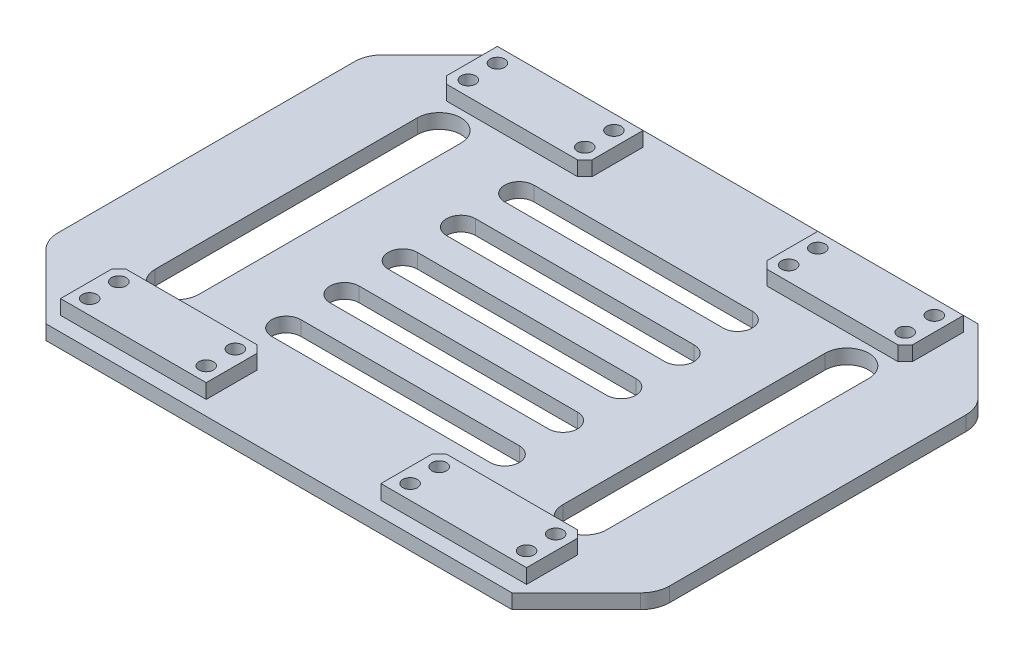
SolidWorks part; units mm, degrees
ref_plane "Front Plane" through (0, 0, 0) normal (0, 0, 1) x (1, 0, 0)
ref_plane "Top Plane" through (0, 0, 0) normal (0, 1, 0) x (1, 0, 0)
ref_plane "Right Plane" through (0, 0, 0) normal (1, 0, 0) x (0, 0, -1)
sketch "Sketch1" plane through (0, 0, 0) normal (0, 0, 1) x (1, 0, 0)
  circle A0 centre (0, 0) radius 18.5
  dimension "D1" = 37
extrude "Boss-Extrude1" add sketch "Sketch1" along normal blind 22.5
sketch "Sketch2" plane through (0, 0, 22.5) normal (0, 0, 1) x (1, 0, 0)
  line L0 (-18.5, 0) -> (18.5, 0) construction
  line L1 (0, 18.5) -> (0, -18.5) construction
  line L2 (11.1332, 19.2832) -> (-10.7359, -18.5952) construction
  line L3 (-11.3747, 19.7016) -> (11.6905, -20.2486) construction
  circle A0 centre (0, 0) radius 18.5 construction
  circle A1 centre (0, 0) radius 15.5 construction
  circle A2 centre (-7.75, 13.4234) radius 1.6
  circle A3 centre (7.75, 13.4234) radius 1.6
  circle A4 centre (-15.5, 0) radius 1.6
  circle A5 centre (-7.75, -13.4234) radius 1.6
  circle A6 centre (7.75, -13.4234) radius 1.6
  circle A7 centre (15.5, 0) radius 1.6
  dimension "D3" = 31
  dimension "D4" = 3.2
  dimension "D1" = 120
  dimension "D2" = 120
extrude "Cut-Extrude1" cut sketch "Sketch2" against normal blind 3.5
sketch "Sketch3" plane through (0, 0, 22.5) normal (0, 0, 1) x (1, 0, 0)
  line L0 (0, 0) -> (0, 18.5) construction
  circle A0 centre (0, 0) radius 18.5 construction
  circle A1 centre (0, 7) radius 6
  circle A2 centre (0, 7) radius 3
  dimension "D1" = 12
  dimension "D3" = 6
  dimension "D2" = 7
extrude "Boss-Extrude2" add sketch "Sketch3" along normal blind 36.3 contours A2 L0 | L0 A2 region at (-1.2732, 7, 22.5) region at (1.2732, 7, 22.5)
extrude "Boss-Extrude3" add sketch "Sketch3<3>" along normal blind 6.3 contours A1 L0 A2 | L0 A1 A2 region at (-5.8658, 7, 22.5) region at (0.1342, 2.5, 22.5)
sketch "Sketch3<3>" plane through (0, 0, 22.5) normal (0, 0, 1) x (1, 0, 0) same geometry as "Sketch3"
sketch "Sketch4" plane through (0, 0, 0) normal (0, 0, -1) x (-1, 0, 0)
  circle A0 centre (0, 0) radius 14.5
  dimension "D1" = 29
extrude "Boss-Extrude4" add sketch "Sketch4" along normal blind 37.8
sketch "Sketch5" plane through (0, 0, -37.8) normal (0, 0, -1) x (-1, 0, 0)
  line L0 (-14.5, 0) -> (14.5, 0) construction
  circle A0 centre (0, 0) radius 5
  circle A1 centre (0, 0) radius 14.5 construction
  dimension "D1" = 10
extrude "Boss-Extrude5" add sketch "Sketch5" along normal blind 3
sketch "Sketch6" plane through (0, 0, -40.8) normal (0, 0, -1) x (-1, 0, 0)
  circle A0 centre (0, 0) radius 1
  dimension "D1" = 2
extrude "Boss-Extrude6" add sketch "Sketch6" along normal blind 9
sketch "Sketch7" plane through (0, 0, -37.8) normal (0, 0, -1) x (-1, 0, 0)
  line L0 (-14.5, 0) -> (14.5, 0) construction
  line L1 (0, 0) -> (0, -10.7163) construction
  line L2 (-12, 1.5) -> (-11.5, 1.5)
  line L3 (-12, 1.5) -> (-12, -1.5)
  line L4 (-12, -1.5) -> (-11.5, -1.5)
  line L5 (-11.5, 1.5) -> (-11.5, -1.5)
  line L6 (12, 1.5) -> (11.5, 1.5)
  line L7 (12, -1.5) -> (11.5, -1.5)
  line L8 (12, 1.5) -> (12, -1.5)
  line L9 (11.5, 1.5) -> (11.5, -1.5)
  circle A0 centre (0, 0) radius 14.5 construction
  circle A1 centre (0, 0) radius 14.5 construction
  dimension "D1" = 3
  dimension "D2" = 1.5
  dimension "D3" = 0.5
  dimension "D4" = 11.5
extrude "Boss-Extrude7" add sketch "Sketch7" along normal blind 6.5
sketch "Sketch8" plane through (12, 0, 0) normal (1, 0, 0) x (0, 0, -1)
  line L0 (42.8651, 0) -> (41.6651, 0) construction
  line L1 (42.8651, -0.3201) -> (41.6651, -0.3201)
  line L2 (42.8651, 0.3201) -> (41.6651, 0.3201)
  line L3 (42.8651, 0) -> (44.3, 0) construction
  line L4 (44.3, 1.5) -> (44.3, -1.5) construction
  arc A0 (42.8651, -0.3201) -> (42.8651, 0.3201) centre (42.8651, 0) ccw
  arc A1 (41.6651, 0.3201) -> (41.6651, -0.3201) centre (41.6651, 0) ccw
  point P2 (42.2651, 0)
  dimension "D1" = 1.2
extrude "Cut-Extrude2" cut sketch "Sketch8" against normal blind 0.5
mirror "Mirror2" about plane through (0, 0, 0) normal (1, 0, 0) of "Cut-Extrude2"
fillet "Fillet1" radius 0.5 4 edges at (-11.75, 1.5, -44.3) (-11.75, -1.5, -44.3) (11.75, 1.5, -44.3) (11.75, -1.5, -44.3)
chamfer "Chamfer1" distance 0.2 angle 45 3 edges at (18.5, 0, 22.5) (6, 7, 28.8) (3, 7, 58.8)
ref_plane "Plane1" through (0, 7, 0) normal (0, 1, 0) x (1, 0, 0)
sketch "Sketch9" plane through (0, 7, 0) normal (0, 1, 0) x (1, 0, 0)
  line L0 (0, -58.6) -> (0, -28.8) construction
  line L1 (3, -58.6) -> (-3, -58.6) construction
  line L2 (-2.8, -58.8) -> (2.8, -58.8) construction
  line L3 (-3, -28.8) -> (3, -28.8) construction
  circle A0 centre (0, -50.8) radius 1.6
  dimension "D1" = 3.2
  dimension "D2" = 8
extrude "Cut-Extrude3" cut sketch "Sketch9" against normal through all and the other way through all
sketch "Sketch10" plane through (0, 0, 22.5) normal (0, 0, 1) x (1, 0, 0)
  circle A0 centre (-7.75, 13.4234) radius 1.6
  circle A1 centre (-15.5, 0) radius 1.6
  circle A2 centre (-7.75, -13.4234) radius 1.6
  circle A3 centre (7.75, -13.4234) radius 1.6
  circle A4 centre (15.5, 0) radius 1.6
  circle A5 centre (7.75, 13.4234) radius 1.6
extrude "Boss-Extrude8" add sketch "Sketch10" along normal blind 10 separate body
sketch "Sketch11" plane through (0, 0, 22.5) normal (0, 0, 1) x (1, 0, 0)
  line L0 (-25, 25) -> (25, 25)
  line L1 (25, 25) -> (25, -35)
  line L2 (25, -35) -> (-25, -35)
  line L3 (-25, -35) -> (-25, 25)
  line L4 (0, -35) -> (0, 25) construction
  dimension "D1" = 60
  dimension "D2" = 50
  dimension "D3" = 50
  dimension "D4" = 25
extrude "Boss-Extrude9" add sketch "Sketch11" along normal blind 5
sketch "Sketch13" plane through (0, 0, 22.5) normal (0, 0, -1) x (-1, 0, 0)
  line L1 (-27.6874, 26.3272) -> (29.1382, 26.3272)
  line L2 (-27.6874, 26.3272) -> (-27.6874, -27.6572)
  line L3 (-27.6874, -27.6572) -> (29.1382, -27.6572)
  line L4 (29.1382, 26.3272) -> (29.1382, -27.6572)
  line L5 (-27.6874, 26.3272) -> (29.1382, -27.6572) construction
  line L6 (-27.6874, -27.6572) -> (29.1382, 26.3272) construction
  point P4 (0.7254, -0.665)
extrude "Cut-Extrude4" cut sketch "Sketch13" along normal blind 121
sketch "Sketch14" plane through (0, 0, 27.5) normal (0, 0, 1) x (1, 0, 0)
  circle A0 centre (-7.75, 13.4234) radius 1.6
  circle A1 centre (7.75, 13.4234) radius 1.6
  circle A2 centre (-15.5, 0) radius 1.6
  circle A3 centre (-7.75, -13.4234) radius 1.6
  circle A4 centre (7.75, -13.4234) radius 1.6
  circle A5 centre (15.5, 0) radius 1.6
  circle A6 centre (0, 7) radius 6
extrude "Cut-Extrude5" cut sketch "Sketch14" against normal through all both and the other way through all
sketch "Sketch15" plane through (0, 25, 0) normal (0, 1, 0) x (1, 0, 0)
  line L1 (-25, -22.5) -> (135, -22.5)
  line L2 (-25, -22.5) -> (-25, -182.5)
  line L3 (-25, -182.5) -> (135, -182.5)
  line L4 (135, -22.5) -> (135, -182.5)
  line L5 (-25, -22.5) -> (135, -182.5) construction
  line L6 (-25, -182.5) -> (135, -22.5) construction
  point P4 (55, -102.5)
  dimension "D1" = 160
  dimension "D2" = 160
extrude "Boss-Extrude10" add sketch "Sketch15" along normal blind 5
sketch "Sketch17" plane through (0, 30, 0) normal (0, 1, 0) x (1, 0, 0)
  line L0 (55, -22.5) -> (55, -182.5) construction
  line L1 (135, -22.5) -> (-25, -22.5) construction
  line L2 (-25, -182.5) -> (135, -182.5) construction
  line L3 (-25, -102.5) -> (135, -102.5) construction
  line L4 (-25, -22.5) -> (-25, -182.5) construction
  line L5 (135, -182.5) -> (135, -22.5) construction
ref_plane "Plane2" through (55, 0, 0) normal (1, 0, 0) x (0, 0, -1)
ref_plane "Plane3" through (0, 0, 102.5) normal (0, 0, 1) x (1, 0, 0)
mirror "Mirror3" about plane through (0, 0, 102.5) normal (0, 0, 1) of bodies 122
mirror "Mirror11" about plane through (55, 0, 0) normal (1, 0, 0) of bodies 123
chamfer "Chamfer2" distance 2.5 angle 45 3 edges at (85, 25, 25) (25, 25, 25) (25, 25, 180)
chamfer "Chamfer3" distance 2.5 angle 45 1 edges at (85, 25, 180)
sketch "Sketch18" plane through (0, 30, 0) normal (0, 1, 0) x (1, 0, 0)
  line L0 (55, -22.5) -> (55, -182.5) construction
  line L1 (135, -22.5) -> (-25, -22.5) construction
  line L2 (-25, -182.5) -> (135, -182.5) construction
  line L3 (17.5, -42.5) -> (92.5, -42.5) construction
  line L4 (17.5, -62.5) -> (92.5, -62.5) construction
  line L5 (17.5, -82.5) -> (92.5, -82.5) construction
  line L6 (17.5, -102.5) -> (92.5, -102.5) construction
  line L7 (17.5, -122.5) -> (92.5, -122.5) construction
  line L8 (17.5, -142.5) -> (92.5, -142.5) construction
  line L9 (92.5, -42.5) -> (17.5, -42.5) construction
  line L10 (92.5, -47.5) -> (17.5, -47.5)
  line L11 (92.5, -37.5) -> (17.5, -37.5)
  line L12 (17.5, -62.5) -> (92.5, -62.5) construction
  line L13 (17.5, -57.5) -> (92.5, -57.5)
  line L14 (17.5, -67.5) -> (92.5, -67.5)
  line L15 (17.5, -82.5) -> (92.5, -82.5) construction
  line L16 (17.5, -77.5) -> (92.5, -77.5)
  line L17 (17.5, -87.5) -> (92.5, -87.5)
  line L18 (17.5, -102.5) -> (92.5, -102.5) construction
  line L19 (17.5, -97.5) -> (92.5, -97.5)
  line L20 (17.5, -107.5) -> (92.5, -107.5)
  line L21 (17.5, -122.5) -> (92.5, -122.5) construction
  line L22 (17.5, -117.5) -> (92.5, -117.5)
  line L23 (17.5, -127.5) -> (92.5, -127.5)
  line L24 (17.5, -142.5) -> (92.5, -142.5) construction
  line L25 (17.5, -137.5) -> (92.5, -137.5)
  line L26 (17.5, -147.5) -> (92.5, -147.5)
  line L27 (17.5, -162.5) -> (92.5, -162.5) construction
  line L28 (92.5, -162.5) -> (17.5, -162.5) construction
  line L29 (92.5, -167.5) -> (17.5, -167.5)
  line L30 (92.5, -157.5) -> (17.5, -157.5)
  arc A0 (92.5, -47.5) -> (92.5, -37.5) centre (92.5, -42.5) ccw
  arc A1 (17.5, -37.5) -> (17.5, -47.5) centre (17.5, -42.5) ccw
  arc A2 (17.5, -57.5) -> (17.5, -67.5) centre (17.5, -62.5) ccw
  arc A3 (92.5, -67.5) -> (92.5, -57.5) centre (92.5, -62.5) ccw
  arc A4 (17.5, -77.5) -> (17.5, -87.5) centre (17.5, -82.5) ccw
  arc A5 (92.5, -87.5) -> (92.5, -77.5) centre (92.5, -82.5) ccw
  arc A6 (17.5, -97.5) -> (17.5, -107.5) centre (17.5, -102.5) ccw
  arc A7 (92.5, -107.5) -> (92.5, -97.5) centre (92.5, -102.5) ccw
  arc A8 (17.5, -117.5) -> (17.5, -127.5) centre (17.5, -122.5) ccw
  arc A9 (92.5, -127.5) -> (92.5, -117.5) centre (92.5, -122.5) ccw
  arc A10 (17.5, -137.5) -> (17.5, -147.5) centre (17.5, -142.5) ccw
  arc A11 (92.5, -147.5) -> (92.5, -137.5) centre (92.5, -142.5) ccw
  arc A12 (92.5, -167.5) -> (92.5, -157.5) centre (92.5, -162.5) ccw
  arc A13 (17.5, -157.5) -> (17.5, -167.5) centre (17.5, -162.5) ccw
  point P14 (55, -42.5)
  point P15 (55, -62.5)
  point P16 (55, -82.5)
  point P17 (55, -122.5)
  point P20 (55, -102.5)
  point P23 (55, -142.5)
  point P24 (55, -42.5)
  point P29 (55, -62.5)
  point P34 (55, -82.5)
  point P39 (55, -102.5)
  point P44 (55, -122.5)
  point P49 (55, -142.5)
  point P54 (55, -162.5)
  point P56 (55, -162.5)
  dimension "D2" = 5
  dimension "D3" = 5
  dimension "D4" = 5
  dimension "D5" = 5
  dimension "D7" = 5
  dimension "D8" = 5
  dimension "D14" = 5
  dimension "D1" = 75
  dimension "D6" = 20
  dimension "D9" = 20
  dimension "D10" = 20
  dimension "D11" = 20
  dimension "D12" = 20
  dimension "D13" = 20
  dimension "D15" = 20
extrude "Cut-Extrude6" cut sketch "Sketch18" against normal through all
sketch "Sketch19" plane through (0, 30, 0) normal (0, 1, 0) x (1, 0, 0)
  line L0 (-25, -182.5) -> (135, -182.5) construction
  line L1 (-25, -22.5) -> (-50, -22.5)
  line L2 (-25, -22.5) -> (-25, -182.5)
  line L3 (-25, -182.5) -> (-50, -182.5)
  line L4 (-50, -22.5) -> (-50, -182.5)
  line L5 (-25, -22.5) -> (-50, -182.5) construction
  line L6 (-25, -182.5) -> (-50, -22.5) construction
  line L8 (135, -22.5) -> (160, -22.5)
  line L9 (135, -22.5) -> (135, -182.5)
  line L10 (135, -182.5) -> (160, -182.5)
  line L11 (160, -22.5) -> (160, -182.5)
  line L12 (135, -22.5) -> (160, -182.5) construction
  line L13 (135, -182.5) -> (160, -22.5) construction
  point P4 (-37.5, -102.5)
  point P12 (147.5, -102.5)
  dimension "D1" = 25
extrude "Boss-Extrude11" add sketch "Sketch19" against normal up to surface (5 mm away) up to face at (55, 25, 42.5)
chamfer "Chamfer4" distance 25 angle 45 4 edges at (-50, 27.5, 22.5) (-50, 27.5, 182.5) (160, 27.5, 182.5) (160, 27.5, 22.5)
sketch "Sketch20" plane through (0, 30, 0) normal (0, 1, 0) x (1, 0, 0)
  line L0 (55, -22.5) -> (55, -182.5) construction
  line L1 (135, -22.5) -> (-25, -22.5) construction
  line L2 (-25, -182.5) -> (135, -182.5) construction
  line L3 (-50, -102.5) -> (160, -102.5) construction
  line L4 (-50, -47.5) -> (-50, -157.5) construction
  line L5 (160, -157.5) -> (160, -47.5) construction
  circle A0 centre (130, -102.5) radius 12.5
  circle A1 centre (130, -62.5) radius 7.5
  circle A2 centre (130, -142.5) radius 7.5
  circle A3 centre (-20, -142.5) radius 7.5
  circle A4 centre (-20, -102.5) radius 12.5
  circle A5 centre (-20, -62.5) radius 7.5
  point P16 (0, 0)
  point P17 (0, 0)
  point P26 (55, -102.5)
  dimension "D3" = 25
  dimension "D4" = 15
  dimension "D1" = 75
  dimension "D2" = 40
extrude "Cut-Extrude7" cut sketch "Sketch20" against normal blind 10
chamfer "Chamfer5" distance 2.5 angle 45 4 edges at (108.75, 25, 177.5) (1.25, 25, 177.5) (1.25, 25, 27.5) (108.75, 25, 27.5)
chamfer "Chamfer6" distance 2.5 angle 45 4 edges at (135, 25, 178.75) (135, 25, 26.25) (-25, 25, 26.25) (-25, 25, 178.75)
fillet "Fillet2" radius 10 4 edges at (-50, 27.5, 157.5) (-50, 27.5, 47.5) (160, 27.5, 47.5) (160, 27.5, 157.5)
sketch "Sketch21" plane through (0, -35, 0) normal (0, -1, 0) x (1, 0, 0)
  line L0 (135, 27.5) -> (135, 22.5) construction
  line L1 (85, 27.5) -> (135, 27.5)
  line L2 (85, 27.5) -> (85, 47.5)
  line L3 (85, 47.5) -> (135, 47.5)
  line L4 (135, 27.5) -> (135, 47.5)
  line L5 (85, 27.5) -> (135, 47.5) construction
  line L6 (85, 47.5) -> (135, 27.5) construction
  line L7 (55, 22.5) -> (55, 152.5338) construction
  line L8 (82.5, 22.5) -> (27.5, 22.5) construction
  line L9 (-50, 102.5) -> (115.8543, 102.5) construction
  line L10 (-50, 153.3579) -> (-50, 51.6421) construction
  line L11 (110, 37.5) -> (110, 45.6589) construction
  line L12 (110, 37.5) -> (99.3164, 37.5) construction
  line L13 (85, 157.5) -> (135, 157.5)
  line L14 (135, 177.5) -> (135, 157.5)
  line L15 (85, 177.5) -> (135, 177.5)
  line L16 (85, 177.5) -> (85, 157.5)
  line L17 (25, 177.5) -> (-25, 177.5)
  line L18 (25, 177.5) -> (25, 157.5)
  line L19 (25, 157.5) -> (-25, 157.5)
  line L20 (-25, 177.5) -> (-25, 157.5)
  line L21 (-25, 27.5) -> (-25, 47.5)
  line L22 (25, 27.5) -> (-25, 27.5)
  line L23 (25, 47.5) -> (-25, 47.5)
  line L24 (25, 27.5) -> (25, 47.5)
  circle A0 centre (90, 32.5) radius 2.5
  circle A1 centre (90, 42.5) radius 2.5
  circle A2 centre (130, 32.5) radius 2.5
  circle A3 centre (130, 42.5) radius 2.5
  circle A4 centre (90, 162.5) radius 2.5
  circle A5 centre (90, 172.5) radius 2.5
  circle A6 centre (130, 172.5) radius 2.5
  circle A7 centre (130, 162.5) radius 2.5
  circle A8 centre (-20, 162.5) radius 2.5
  circle A9 centre (-20, 172.5) radius 2.5
  circle A10 centre (20, 172.5) radius 2.5
  circle A11 centre (20, 162.5) radius 2.5
  circle A12 centre (-20, 32.5) radius 2.5
  circle A13 centre (-20, 42.5) radius 2.5
  circle A14 centre (20, 32.5) radius 2.5
  circle A15 centre (20, 42.5) radius 2.5
  point P4 (110, 37.5)
  dimension "D4" = 5
  dimension "D1" = 20
  dimension "D2" = 5
  dimension "D3" = 20
extrude "Boss-Extrude12" add sketch "Sketch21" against normal blind 5 from offset 5 offset against normal yes
chamfer "Chamfer7" distance 2.5 angle 45 8 edges at (85, -27.5, 47.5) (135, -27.5, 47.5) (-25, -27.5, 47.5) (25, -27.5, 47.5) (25, -27.5, 157.5) (-25, -27.5, 157.5) (85, -27.5, 157.5) (135, -27.5, 157.5)
sketch "Sketch22" plane through (0, -35, 0) normal (0, -1, 0) x (1, 0, 0)
  line L0 (-27.5, 180) -> (-25, 182.5)
  line L1 (-25, 182.5) -> (27.5, 182.5)
  line L2 (82.5, 182.5) -> (135, 182.5)
  line L3 (135, 182.5) -> (137.5, 180)
  line L4 (137.5, 25) -> (135, 22.5)
  line L5 (135, 22.5) -> (82.5, 22.5)
  line L6 (-27.5, 25) -> (-25, 22.5)
  line L7 (-25, 22.5) -> (27.5, 22.5)
  line L8 (-22.5, 157.5) -> (22.5, 157.5) construction
  line L9 (22.5, 157.5) -> (25, 160) construction
  line L10 (25, 160) -> (25, 177.5) construction
  line L11 (25, 177.5) -> (-25, 177.5) construction
  line L12 (-25, 177.5) -> (-25, 160) construction
  line L13 (-25, 160) -> (-22.5, 157.5) construction
  line L14 (85, 177.5) -> (85, 160) construction
  line L15 (85, 160) -> (87.5, 157.5) construction
  line L16 (87.5, 157.5) -> (132.5, 157.5) construction
  line L17 (132.5, 157.5) -> (135, 160) construction
  line L18 (135, 160) -> (135, 177.5) construction
  line L19 (135, 177.5) -> (85, 177.5) construction
  line L20 (-27.5, 180) -> (-47.0711, 160.4289)
  line L21 (-50, 153.3579) -> (-50, 51.6421)
  line L22 (-47.0711, 44.5711) -> (-27.5, 25)
  line L23 (-27.5, 25) -> (-27.5, 30)
  line L24 (-27.5, 30) -> (27.5, 30)
  line L25 (27.5, 30) -> (27.5, 22.5)
  line L26 (27.5, 22.5) -> (82.5, 22.5)
  line L27 (82.5, 22.5) -> (82.5, 30)
  line L28 (82.5, 30) -> (137.5, 30)
  line L29 (137.5, 30) -> (137.5, 25)
  line L30 (137.5, 25) -> (157.0711, 44.5711)
  line L31 (160, 51.6421) -> (160, 153.3579)
  line L32 (157.0711, 160.4289) -> (137.5, 180)
  line L33 (137.5, 180) -> (137.5, 175)
  line L34 (137.5, 175) -> (82.5, 175)
  line L35 (82.5, 175) -> (82.5, 182.5)
  line L36 (82.5, 182.5) -> (27.5, 182.5)
  line L37 (27.5, 182.5) -> (27.5, 175)
  line L38 (27.5, 175) -> (-27.5, 175)
  line L39 (-27.5, 175) -> (-27.5, 180)
  line L40 (-27.5, 180) -> (-47.0711, 160.4289)
  line L41 (-50, 153.3579) -> (-50, 51.6421)
  line L42 (-47.0711, 44.5711) -> (-27.5, 25)
  line L46 (27.5, 22.5) -> (82.5, 22.5)
  line L50 (137.5, 25) -> (157.0711, 44.5711)
  line L51 (160, 51.6421) -> (160, 153.3579)
  line L52 (157.0711, 160.4289) -> (137.5, 180)
  line L56 (82.5, 182.5) -> (27.5, 182.5)
  line L60 (132.5, 47.5) -> (87.5, 47.5) construction
  line L61 (87.5, 47.5) -> (85, 45) construction
  line L62 (85, 45) -> (85, 27.5) construction
  line L63 (85, 27.5) -> (135, 27.5) construction
  line L64 (135, 27.5) -> (135, 45) construction
  line L65 (135, 45) -> (132.5, 47.5) construction
  line L66 (25, 27.5) -> (25, 45) construction
  line L67 (25, 45) -> (22.5, 47.5) construction
  line L68 (-22.5, 47.5) -> (-25, 45) construction
  line L69 (22.5, 47.5) -> (-22.5, 47.5) construction
  line L70 (-25, 45) -> (-25, 27.5) construction
  line L71 (-25, 27.5) -> (25, 27.5) construction
  line L72 (-22.5, 157.5) -> (22.5, 157.5)
  line L73 (22.5, 157.5) -> (25, 160)
  line L74 (25, 160) -> (25, 177.5)
  line L75 (25, 177.5) -> (-25, 177.5)
  line L76 (-25, 177.5) -> (-25, 160)
  line L77 (-25, 160) -> (-22.5, 157.5)
  line L78 (85, 177.5) -> (85, 160)
  line L79 (85, 160) -> (87.5, 157.5)
  line L80 (87.5, 157.5) -> (132.5, 157.5)
  line L81 (132.5, 157.5) -> (135, 160)
  line L82 (135, 160) -> (135, 177.5)
  line L83 (135, 177.5) -> (85, 177.5)
  line L84 (132.5, 47.5) -> (87.5, 47.5)
  line L85 (87.5, 47.5) -> (85, 45)
  line L86 (85, 45) -> (85, 27.5)
  line L87 (85, 27.5) -> (135, 27.5)
  line L88 (135, 27.5) -> (135, 45)
  line L89 (135, 45) -> (132.5, 47.5)
  line L90 (25, 27.5) -> (25, 45)
  line L91 (25, 45) -> (22.5, 47.5)
  line L92 (-22.5, 47.5) -> (-25, 45)
  line L93 (22.5, 47.5) -> (-22.5, 47.5)
  line L94 (-25, 45) -> (-25, 27.5)
  line L95 (-25, 27.5) -> (25, 27.5)
  circle A0 centre (20, 42.5) radius 2.5 construction
  circle A1 centre (20, 32.5) radius 2.5 construction
  circle A2 centre (-20, 32.5) radius 2.5 construction
  circle A3 centre (-20, 42.5) radius 2.5 construction
  arc A4 (-47.0711, 160.4289) -> (-50, 153.3579) centre (-40, 153.3579) ccw
  arc A5 (-50, 51.6421) -> (-47.0711, 44.5711) centre (-40, 51.6421) ccw
  arc A6 (157.0711, 44.5711) -> (160, 51.6421) centre (150, 51.6421) ccw
  arc A7 (160, 153.3579) -> (157.0711, 160.4289) centre (150, 153.3579) ccw
  arc A8 (-47.0711, 160.4289) -> (-50, 153.3579) centre (-40, 153.3579) ccw
  arc A9 (-50, 51.6421) -> (-47.0711, 44.5711) centre (-40, 51.6421) ccw
  arc A10 (157.0711, 44.5711) -> (160, 51.6421) centre (150, 51.6421) ccw
  arc A11 (160, 153.3579) -> (157.0711, 160.4289) centre (150, 153.3579) ccw
  circle A12 centre (20, 172.5) radius 2.5 construction
  circle A13 centre (130, 42.5) radius 2.5 construction
  circle A14 centre (130, 32.5) radius 2.5 construction
  circle A15 centre (90, 32.5) radius 2.5 construction
  circle A16 centre (90, 42.5) radius 2.5 construction
  circle A17 centre (130, 162.5) radius 2.5 construction
  circle A18 centre (130, 172.5) radius 2.5 construction
  circle A19 centre (-20, 172.5) radius 2.5 construction
  circle A20 centre (-20, 162.5) radius 2.5 construction
  circle A21 centre (20, 162.5) radius 2.5 construction
  circle A22 centre (90, 162.5) radius 2.5 construction
  circle A23 centre (90, 172.5) radius 2.5 construction
  circle A24 centre (20, 42.5) radius 2.5
  circle A25 centre (20, 32.5) radius 2.5
  circle A26 centre (-20, 32.5) radius 2.5
  circle A27 centre (-20, 42.5) radius 2.5
  circle A28 centre (20, 172.5) radius 2.5
  circle A29 centre (130, 42.5) radius 2.5
  circle A30 centre (130, 32.5) radius 2.5
  circle A31 centre (90, 32.5) radius 2.5
  circle A32 centre (90, 42.5) radius 2.5
  circle A33 centre (130, 162.5) radius 2.5
  circle A34 centre (130, 172.5) radius 2.5
  circle A35 centre (-20, 172.5) radius 2.5
  circle A36 centre (-20, 162.5) radius 2.5
  circle A37 centre (20, 162.5) radius 2.5
  circle A38 centre (90, 162.5) radius 2.5
  circle A39 centre (90, 172.5) radius 2.5
  line M25 (135, 182.5) -> (85, 182.5)
  line M26 (85, 182.5) -> (85, 177.5)
  line M27 (85, 177.5) -> (135, 177.5)
  line M28 (135, 177.5) -> (135, 182.5)
  dimension "D1" = 0
extrude "Boss-Extrude13" add sketch "Sketch22" along normal blind 5 separate body contours L51 A11 L52 L3 L82 L81 L80 L79 L78 L2 L56 L1 L0 L40 A8 L41 A9 L42 L6 L7 L46 L5 L4 L50 A10 L77 L76 L75 L74 L73 L72 L89 L88 L87 L86 L85 L84 L95 L94 L92 L93 L91 L90 M28 M26 | L94 L95 L90 L91 L93 L92 A27 A26 A25 A24 | L88 L89 L84 L85 L86 L87 A32 A31 A30 A29 | L81 L82 L78 L79 L80 A39 A38 A34 A33 M27 | L76 L77 L72 L73 L74 L75 A37 A36 A35 A28 | M28 M25 M26 M27 region at (55, -35, 102.5) region at (0.293, -35, 179.8168) region at (0, -35, 176.25) region at (0, -35, 166.1884) region at (83.75, -35, 178.75) region at (110, -35, 180) region at (136.1667, -35, 178.1667) region at (110, -35, 176.25) region at (110, -35, 166.1884) region at (0.293, -35, 25.1832) region at (0, -35, 38.8116) region at (0, -35, 28.75) region at (109.707, -35, 25.1832) region at (110, -35, 38.8116) region at (110, -35, 28.75)
sketch "Sketch23" plane through (0, 0, 22.5) normal (0, 0, -1) x (-1, 0, 0)
  line L1 (-160, -35) -> (71.3507, -35)
  line L2 (-160, -35) -> (-160, 61.0202)
  line L3 (-160, 61.0202) -> (71.3507, 61.0202)
  line L4 (71.3507, -35) -> (71.3507, 61.0202)
  line L5 (-160, -35) -> (71.3507, 61.0202) construction
  line L6 (-160, 61.0202) -> (71.3507, -35) construction
  point P4 (-44.3246, 13.0101)
extrude "Cut-Extrude8" cut sketch "Sketch23" against normal blind 212
extrude "Boss-Extrude14" add sketch "Sketch22<3>" against normal blind 5 contours L88 L89 L84 L85 L86 L87 A32 A31 A30 A29 | L94 L95 L90 L91 L93 L92 A27 A26 A25 A24 | L81 L82 L78 L79 L80 A39 A38 A34 A33 M27 | L76 L77 L72 L73 L74 L75 A37 A36 A35 A28 region at (0, -35, 176.25) region at (0, -35, 166.1884) region at (110, -35, 176.25) region at (110, -35, 166.1884) region at (0, -35, 38.8116) region at (0, -35, 28.75) region at (110, -35, 38.8116) region at (110, -35, 28.75)
sketch "Sketch22<3>" plane through (0, -35, 0) normal (0, -1, 0) x (1, 0, 0) same geometry as "Sketch22"
sketch "Sketch24" plane through (0, -35, 0) normal (0, 1, 0) x (1, 0, 0)
  line L0 (55, -22.5) -> (55, -182.5) construction
  line L1 (-25, -22.5) -> (135, -22.5) construction
  line L2 (-25, -182.5) -> (135, -182.5) construction
  line L3 (-50, -102.5) -> (160, -102.5) construction
  line L4 (-50, -153.3579) -> (-50, -51.6421) construction
  line L6 (17.5, -62.5) -> (92.5, -62.5) construction
  line L7 (160, -51.6421) -> (160, -153.3579) construction
  line L8 (17.5, -82.5) -> (92.5, -82.5) construction
  line L9 (17.5, -62.5) -> (92.5, -62.5) construction
  line L10 (17.5, -102.5) -> (92.5, -102.5) construction
  line L11 (17.5, -57.5) -> (92.5, -57.5)
  line L12 (17.5, -122.5) -> (92.5, -122.5) construction
  line L13 (17.5, -67.5) -> (92.5, -67.5)
  line L14 (17.5, -142.5) -> (92.5, -142.5) construction
  line L15 (92.5, -82.5) -> (17.5, -82.5) construction
  line L16 (92.5, -87.5) -> (17.5, -87.5)
  line L17 (92.5, -77.5) -> (17.5, -77.5)
  line L18 (17.5, -102.5) -> (92.5, -102.5) construction
  line L19 (17.5, -97.5) -> (92.5, -97.5)
  line L20 (17.5, -107.5) -> (92.5, -107.5)
  line L21 (92.5, -122.5) -> (17.5, -122.5) construction
  line L22 (92.5, -127.5) -> (17.5, -127.5)
  line L23 (92.5, -117.5) -> (17.5, -117.5)
  line L24 (17.5, -142.5) -> (92.5, -142.5) construction
  line L25 (17.5, -137.5) -> (92.5, -137.5)
  line L26 (17.5, -147.5) -> (92.5, -147.5)
  line L27 (125, -57.5) -> (125, -147.5) construction
  line L28 (-15, -57.5) -> (-15, -147.5) construction
  line L29 (-15, -57.5) -> (-15, -147.5) construction
  line L30 (-7.5, -57.5) -> (-7.5, -147.5)
  line L31 (-22.5, -57.5) -> (-22.5, -147.5)
  line L32 (125, -57.5) -> (125, -147.5) construction
  line L33 (132.5, -57.5) -> (132.5, -147.5)
  line L34 (117.5, -57.5) -> (117.5, -147.5)
  arc A0 (17.5, -57.5) -> (17.5, -67.5) centre (17.5, -62.5) ccw
  arc A1 (92.5, -67.5) -> (92.5, -57.5) centre (92.5, -62.5) ccw
  arc A2 (92.5, -87.5) -> (92.5, -77.5) centre (92.5, -82.5) ccw
  arc A3 (17.5, -77.5) -> (17.5, -87.5) centre (17.5, -82.5) ccw
  arc A4 (17.5, -97.5) -> (17.5, -107.5) centre (17.5, -102.5) ccw
  arc A5 (92.5, -107.5) -> (92.5, -97.5) centre (92.5, -102.5) ccw
  arc A6 (92.5, -127.5) -> (92.5, -117.5) centre (92.5, -122.5) ccw
  arc A7 (17.5, -117.5) -> (17.5, -127.5) centre (17.5, -122.5) ccw
  arc A8 (17.5, -137.5) -> (17.5, -147.5) centre (17.5, -142.5) ccw
  arc A9 (92.5, -147.5) -> (92.5, -137.5) centre (92.5, -142.5) ccw
  arc A10 (-7.5, -57.5) -> (-22.5, -57.5) centre (-15, -57.5) ccw
  arc A11 (-22.5, -147.5) -> (-7.5, -147.5) centre (-15, -147.5) ccw
  arc A12 (132.5, -57.5) -> (117.5, -57.5) centre (125, -57.5) ccw
  arc A13 (117.5, -147.5) -> (132.5, -147.5) centre (125, -147.5) ccw
  point P7 (55, -62.5)
  point P10 (55, -82.5)
  point P11 (55, -102.5)
  point P21 (55, -122.5)
  point P23 (55, -142.5)
  point P27 (55, -62.5)
  point P32 (55, -82.5)
  point P37 (55, -102.5)
  point P42 (55, -122.5)
  point P47 (55, -142.5)
  point P56 (-15, -102.5)
  point P61 (125, -102.5)
  dimension "D6" = 5
  dimension "D7" = 5
  dimension "D8" = 5
  dimension "D9" = 5
  dimension "D10" = 5
  dimension "D14" = 7.5
  dimension "D15" = 7.5
  dimension "D1" = 20
  dimension "D2" = 20
  dimension "D3" = 20
  dimension "D4" = 20
  dimension "D5" = 75
  dimension "D11" = 90
  dimension "D12" = 45
  dimension "D13" = 45
  dimension "D16" = 140
  dimension "D17" = 70
extrude "Cut-Extrude9" cut sketch "Sketch24" against normal through all both and the other way through all
